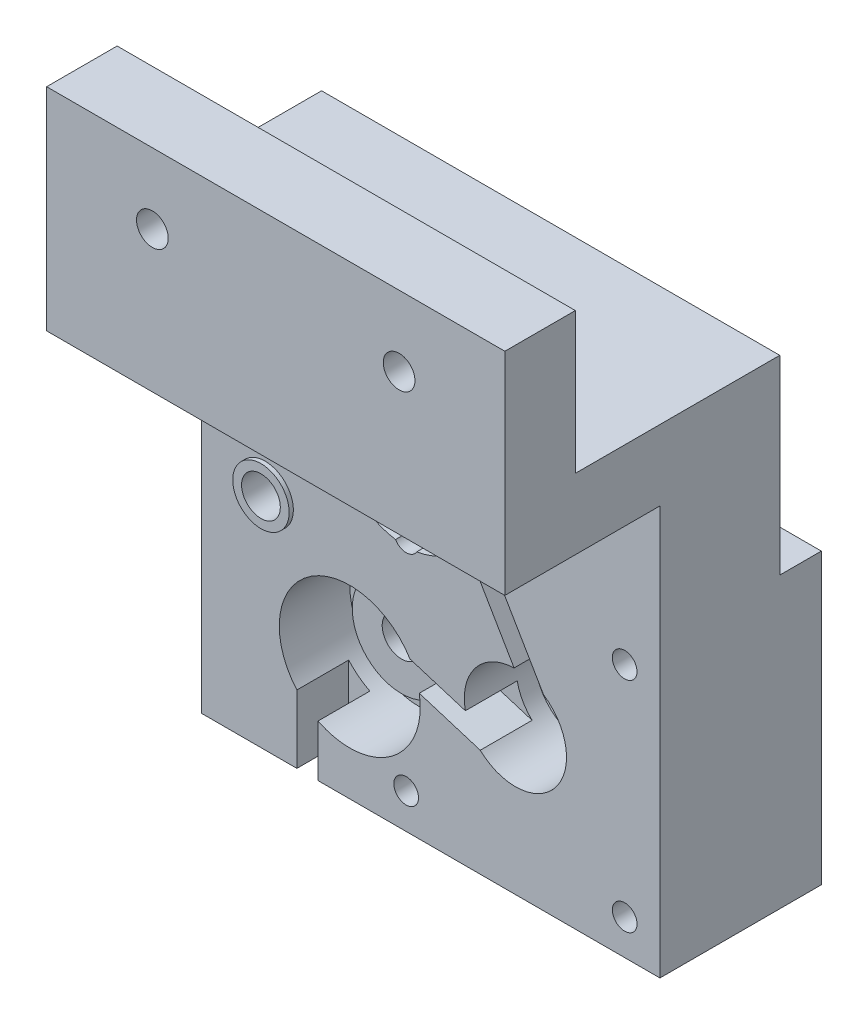
SolidWorks part; units mm, degrees
ref_plane "Front Plane" through (0, 0, 0) normal (0, 0, 1) x (1, 0, 0)
ref_plane "Top Plane" through (0, 0, 0) normal (0, 1, 0) x (1, 0, 0)
ref_plane "Right Plane" through (0, 0, 0) normal (1, 0, 0) x (0, 0, -1)
sketch "Sketch1" plane through (0, 0, 0) normal (0, 0, 1) x (1, 0, 0)
  line L1 (-44.5, 47.5) -> (20.5, 47.5)
  line L2 (-44.5, 47.5) -> (-44.5, -20.5)
  line L3 (-44.5, -20.5) -> (20.5, -20.5)
  line L4 (20.5, 47.5) -> (20.5, -20.5)
  circle A0 centre (0, 0) radius 12
  circle A1 centre (-15.5, 15.5) radius 1.75
  circle A2 centre (15.5, 15.5) radius 1.75
  circle A3 centre (15.5, -15.5) radius 1.75
  circle A4 centre (-15.5, -15.5) radius 1.75
  circle A6 centre (-15.5, 24.5) radius 2.75
  dimension "D1" = 24
  dimension "D2" = 31
  dimension "D3" = 31
  dimension "D4" = 31
  dimension "D5" = 31
  dimension "D6" = 15.5
  dimension "D7" = 15.5
  dimension "D8" = 0
  dimension "D9" = 3.5
  dimension "D10" = 3.5
  dimension "D11" = 3.5
  dimension "D12" = 3.5
  dimension "D13" = 23
  dimension "D14" = 29
  dimension "D16" = 5.5
  dimension "D21" = 47.5
  dimension "D22" = 44.5
  dimension "D19" = 65
  dimension "D20" = 68
extrude "Boss-Extrude1" add sketch "Sketch1" along normal blind 7
sketch "Sketch2" plane through (0, 0, 7) normal (0, 0, 1) x (1, 0, 0)
  line L0 (20.5, 47.5) -> (-44.5, 47.5) construction
  line L1 (-44.5, 47.5) -> (-44.5, -20.5) construction
  circle A0 centre (-15.5, 24.5) radius 2.75
  circle A6 centre (-35.5, 11) radius 2.75
  circle A8 centre (-23.5, -4.2471) radius 2.75
  circle A9 centre (-23.5, -4.2471) radius 7
  circle A10 centre (-15.5, 24.5) radius 7
  circle A11 centre (-35.5, 11) radius 4
  dimension "D1" = 14
  dimension "D2" = 5.5
  dimension "D3" = 5.5
  dimension "D4" = 8
  dimension "D6" = 14
  dimension "D5" = 23
  dimension "D8" = 29
  dimension "D9" = 36.5
  dimension "D10" = 9
  dimension "D11" = 51.7471
  dimension "D7" = 21
extrude "Boss-Extrude2" add sketch "Sketch2" along normal blind 2.65
sketch "Sketch3" plane through (20.5, 0, 0) normal (1, 0, 0) x (0, 0, -1)
  line L1 (-7, 47.5) -> (-29, 47.5)
  line L2 (-7, 47.5) -> (-7, 37.5)
  line L3 (-7, 37.5) -> (-29, 37.5)
  line L4 (-29, 47.5) -> (-29, 37.5)
  line L5 (-29, 37.5) -> (-39, 37.5)
  line L6 (-29, 37.5) -> (-29, 67.5)
  line L7 (-29, 67.5) -> (-39, 67.5)
  line L8 (-39, 37.5) -> (-39, 67.5)
  line M7 (-7, 47.5) -> (-7, -20.5)
  dimension "D1" = 22
  dimension "D2" = 10
  dimension "D3" = 20
  dimension "D4" = 10
extrude "Boss-Extrude3" add sketch "Sketch3" against normal through all contours L1 L4 L3 M7 | L8 L5 L4 L6 L7 region at (20.5, 42.5, 18) region at (20.5, 52.5, 34)
sketch "Sketch4" plane through (0, 0, 39) normal (0, 0, 1) x (1, 0, 0)
  line L0 (-44.5, 37.5) -> (20.5, 37.5) construction
  line L1 (-44.5, 67.5) -> (20.5, 67.5) construction
  line L2 (-44.5, 37.5) -> (-44.5, 67.5) construction
  line L3 (20.5, 37.5) -> (20.5, 67.5) construction
  circle A0 centre (-29.5, 57.5) radius 2.25
  circle A1 centre (5.5, 57.5) radius 2.25
  dimension "D1" = 4.5
  dimension "D2" = 20
  dimension "D3" = 10
  dimension "D4" = 15
  dimension "D5" = 10
  dimension "D6" = 15
  dimension "D7" = 4.5
extrude "Cut-Extrude1" cut sketch "Sketch4" against normal blind 10
sketch "Sketch5" plane through (0, 37.5, 0) normal (0, -1, 0) x (1, 0, 0)
  line L0 (-44.5, 7) -> (-44.5, 39) construction
  line L1 (-44.5, 39) -> (20.5, 39) construction
  line L2 (20.5, 7) -> (20.5, 39) construction
  circle A0 centre (-29.5, 19) radius 2.25
  circle A1 centre (5.5, 19) radius 2.25
  dimension "D1" = 15
  dimension "D2" = 20
  dimension "D3" = 20
  dimension "D4" = 15
  dimension "D5" = 4.5
  dimension "D6" = 4.5
extrude "Cut-Extrude2" cut sketch "Sketch5" against normal blind 10
sketch "Sketch7" plane through (0, 0, 0) normal (0, 0, -1) x (-1, 0, 0)
  line L1 (-20.5, -20.5) -> (20.5, -20.5)
  line L2 (-20.5, -20.5) -> (-20.5, 20.5)
  line L3 (-20.5, 20.5) -> (20.5, 20.5)
  line L4 (20.5, -20.5) -> (20.5, 20.5)
  circle A0 centre (0, 0) radius 12
  circle A1 centre (-15.5, 15.5) radius 1.75
  circle A2 centre (15.5, 15.5) radius 1.75
  circle A3 centre (15.5, -15.5) radius 1.75
  circle A4 centre (-15.5, -15.5) radius 1.75
  dimension "D2" = 5
  dimension "D3" = 5
  dimension "D4" = 5
  dimension "D1" = 5
extrude "Boss-Extrude5" add sketch "Sketch7" along normal blind 5.9
sketch "Sketch8" plane through (0, 0, 9.65) normal (0, 0, 1) x (1, 0, 0)
  circle A0 centre (-35.5, 11) radius 2.75
  circle A1 centre (-35.5, 11) radius 4
  dimension "D1" = 8
extrude "Boss-Extrude6" add sketch "Sketch8" along normal blind 7.95
sketch "Sketch10" plane through (0, 0, 7) normal (0, 0, 1) x (1, 0, 0)
  circle A0 centre (-35.5, 11) radius 2.75
  circle A1 centre (-23.5, -4.2471) radius 2.75
extrude "Cut-Extrude3" cut sketch "Sketch10" against normal blind 9.45
sketch "Sketch11" plane through (0, 0, 7) normal (0, 0, 1) x (1, 0, 0)
  line L1 (-44.5, 37.5) -> (20.5, 37.5)
  line L2 (-44.5, 37.5) -> (-44.5, -20.5)
  line L3 (-44.5, -20.5) -> (20.5, -20.5)
  line L4 (20.5, 37.5) -> (20.5, -20.5)
  circle A0 centre (-23.5, -4.2471) radius 10
  circle A1 centre (-15.5, 24.5) radius 10
  circle A2 centre (-15.5, 24.5) radius 2.75
  circle A3 centre (-23.5, -4.2471) radius 2.75
  circle A4 centre (0, 0) radius 7.25
  circle M1 centre (15.5, -15.5) radius 1.75
  circle M2 centre (-15.5, 15.5) radius 1.75
  circle M3 centre (0, 0) radius 12
  circle M4 centre (15.5, 15.5) radius 1.75
  circle M5 centre (-15.5, -15.5) radius 1.75
  circle M7 centre (-35.5, 11) radius 4
  line M9 (20.5, -20.5) -> (20.5, 37.5)
  line M10 (20.5, 37.5) -> (-44.5, 37.5)
  line M11 (-44.5, 37.5) -> (-44.5, -20.5)
  line M12 (-44.5, -20.5) -> (20.5, -20.5)
  dimension "D1" = 20
  dimension "D2" = 20
  dimension "D3" = 14.5
extrude "Boss-Extrude7" add sketch "Sketch11" along normal blind 10 contours A1 A0 M12 M9 M10 M11 M2 M4 M7 M5 M3 M1 | A4 M3 region at (-12.0095, 9.6819, 7) region at (-11.6606, 0, 7)
sketch "Sketch12" plane through (0, 0, 17) normal (0, 0, 1) x (1, 0, 0)
  line L1 (-11.6164, 26.7733) -> (3.0206, 1.7681)
  line L2 (-44.5, 37.5) -> (-44.5, -20.5) construction
  line L6 (-44.5, -20.5) -> (20.5, -20.5) construction
  line L7 (-44.5, 29) -> (-15.5, 29)
  line L8 (-44.5, 29) -> (-44.5, 32)
  line L9 (-44.5, 32) -> (-15.5, 32)
  line L13 (-9.0274, 28.2888) -> (5.6096, 3.2836)
  line L14 (-21.2843, 2.9181) -> (-1.034, -3.3438)
  line L17 (-22.1706, 0.052) -> (-1.9202, -6.2099)
  line L18 (-31, -4.2471) -> (-31, -20.5)
  line L20 (-31, -20.5) -> (-28, -20.5)
  line L21 (-28, -4.2471) -> (-28, -20.5)
  arc A5 (-21.2843, 2.9181) -> (-31, -4.2471) centre (-23.5, -4.2471) ccw
  arc A6 (-22.1706, 0.052) -> (-28, -4.2471) centre (-23.5, -4.2471) ccw
  arc A7 (-1.034, -3.3438) -> (3.0206, 1.7681) centre (0, 0) ccw
  arc A8 (-11.6164, 26.7733) -> (-15.5, 29) centre (-15.5, 24.5) ccw
  arc A9 (-9.0274, 28.2888) -> (-15.5, 32) centre (-15.5, 24.5) ccw
  arc A10 (-1.9202, -6.2099) -> (5.6096, 3.2836) centre (0, 0) ccw
  dimension "D4" = 3
  dimension "D5" = 3
  dimension "D6" = 3
  dimension "D7" = 3
extrude "Cut-Extrude4" cut sketch "Sketch12" against normal up to surface (7.35 mm away) up to face at (-16.5, -4.2471, 9.65)
